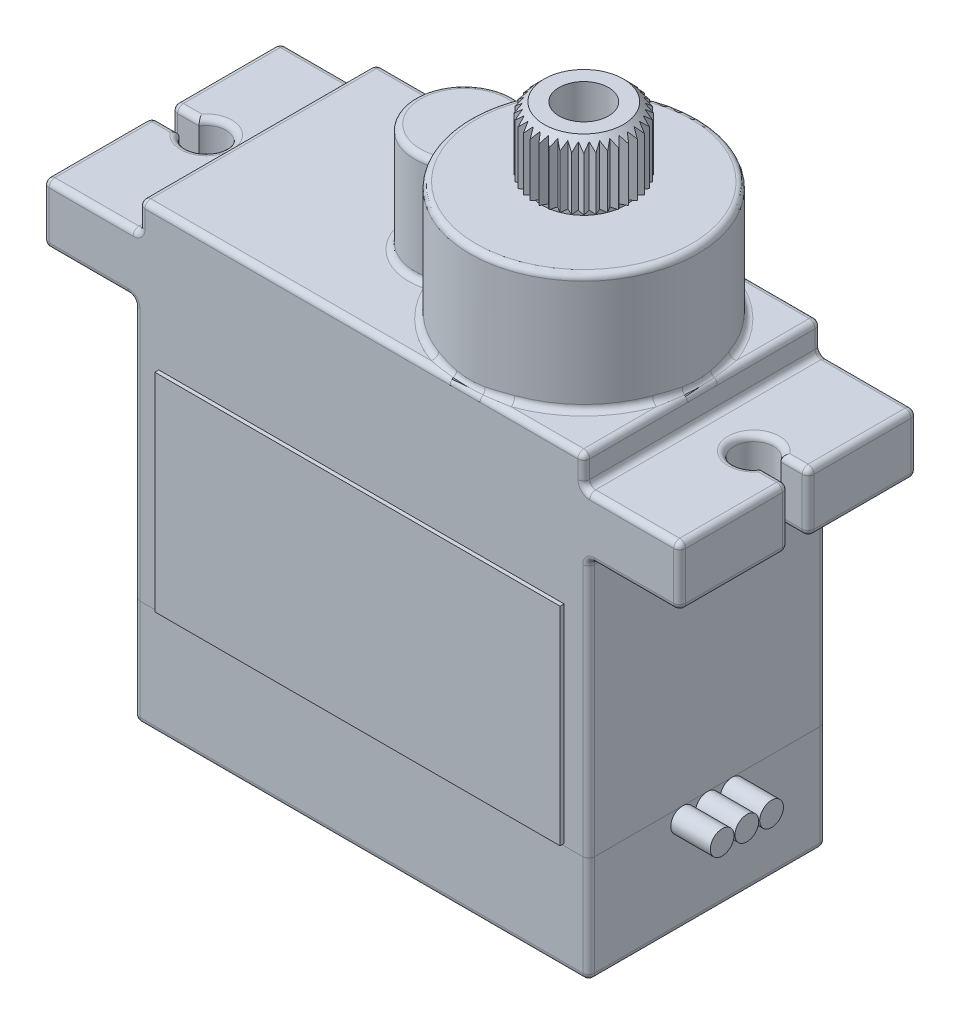
SolidWorks part; units mm, degrees
ref_plane "Front Plane" through (0, 0, 0) normal (0, 0, 1) x (1, 0, 0)
ref_plane "Top Plane" through (0, 0, 0) normal (0, 1, 0) x (1, 0, 0)
ref_plane "Right Plane" through (0, 0, 0) normal (1, 0, 0) x (0, 0, -1)
sketch "Sketch1" plane through (0, 0, 0) normal (0, 1, 0) x (1, 0, 0)
  line L1 (-11.5, -6) -> (11.5, -6)
  line L2 (-11.5, -6) -> (-11.5, 6)
  line L3 (-11.5, 6) -> (11.5, 6)
  line L4 (11.5, -6) -> (11.5, 6)
  line L5 (-11.5, -6) -> (11.5, 6) construction
  line L6 (-11.5, 6) -> (11.5, -6) construction
  point P0 (0, 0)
  dimension "D1" = 12
  dimension "D2" = 23
extrude "Boss-Extrude1" add sketch "Sketch1" along normal blind 18.5
sketch "Sketch2" plane through (0, 18.5, 0) normal (0, 1, 0) x (1, 0, 0)
  line L0 (11.5, 6) -> (-11.5, 6) construction
  line L1 (-16.1, -6) -> (16.1, -6)
  line L2 (-16.1, -6) -> (-16.1, 6)
  line L3 (-16.1, 6) -> (16.1, 6)
  line L4 (16.1, -6) -> (16.1, 6)
  line L5 (-16.1, -6) -> (16.1, 6) construction
  line L6 (-16.1, 6) -> (16.1, -6) construction
  point P0 (0, 0)
  dimension "D1" = 32.2
extrude "Boss-Extrude2" add sketch "Sketch2" along normal blind 3
sketch "Sketch3" plane through (0, 21.5, 0) normal (0, 1, 0) x (1, 0, 0)
  line L0 (16.1, 6) -> (-16.1, 6) construction
  line L1 (-11.25, -6) -> (11.25, -6)
  line L2 (-11.25, -6) -> (-11.25, 6)
  line L3 (-11.25, 6) -> (11.25, 6)
  line L4 (11.25, -6) -> (11.25, 6)
  line L5 (-11.25, -6) -> (11.25, 6) construction
  line L6 (-11.25, 6) -> (11.25, -6) construction
  point P0 (0, 0)
  dimension "D1" = 22.5
extrude "Boss-Extrude3" add sketch "Sketch3" along normal blind 1.5
sketch "Sketch4" plane through (0, 23, 0) normal (0, 1, 0) x (1, 0, 0)
  line L0 (-11.25, 6) -> (-11.25, -6) construction
  line L1 (5.25, 5.75) -> (5.25, 6) construction
  line L2 (11.25, 6) -> (-11.25, 6) construction
  line L3 (11, 0) -> (11.25, 0) construction
  line L4 (11.25, -6) -> (11.25, 6) construction
  line L5 (5.25, -5.75) -> (5.25, -6) construction
  line L6 (-11.25, -6) -> (11.25, -6) construction
  circle A0 centre (5.25, 0) radius 5.75
  point P5 (-11.25, 0)
  dimension "D1" = 11.5
extrude "Boss-Extrude4" add sketch "Sketch4" along normal blind 6
sketch "Sketch5" plane through (0, 23, 0) normal (0, 1, 0) x (1, 0, 0)
  line L0 (-11.25, 6) -> (-11.25, -6) construction
  circle A0 centre (-0.8, 0) radius 2.5
  circle A1 centre (5.25, 0) radius 5.75 construction
  circle A2 centre (5.25, 0) radius 5.75 construction
  point P2 (-3.3, 0)
  point P5 (-11.25, 0)
  point P6 (11, 0)
  dimension "D1" = 5
  dimension "D2" = 14.3
extrude "Boss-Extrude5" add sketch "Sketch5" along normal blind 5.5
sketch "Sketch6" plane through (0, 21.5, 0) normal (0, 1, 0) x (1, 0, 0)
  line L0 (-11.25, 6) -> (-11.25, -6) construction
  line L1 (0, 6) -> (0, -6) construction
  line L2 (11.25, 6) -> (-11.25, 6) construction
  line L3 (-11.25, -6) -> (11.25, -6) construction
  line L4 (-14.716, 0.5) -> (-16.1, 0.5)
  line L5 (-16.1, 6) -> (-16.1, -6) construction
  line L6 (-14.716, -0.5) -> (-16.1, -0.5)
  line L7 (-16.1, 0.5) -> (-16.1, -0.5)
  line L8 (16.1, 0.5) -> (16.1, -0.5)
  line L9 (14.716, -0.5) -> (16.1, -0.5)
  line L10 (14.716, 0.5) -> (16.1, 0.5)
  arc A0 (-14.716, -0.5) -> (-14.716, 0.5) centre (-13.85, 0) ccw
  arc A1 (14.716, -0.5) -> (14.716, 0.5) centre (13.85, 0) cw
  point P4 (-11.25, 0)
  dimension "D1" = 2
  dimension "D2" = 27.7
  dimension "D3" = 1
extrude "Cut-Extrude1" cut sketch "Sketch6" against normal through all
sketch "Sketch7" plane through (0, 29, 0) normal (0, 1, 0) x (1, 0, 0)
  circle A0 centre (5.25, 0) radius 2.5
  dimension "D1" = 5
extrude "Boss-Extrude6" add sketch "Sketch7" along normal blind 3.5
sketch "Sketch8" plane through (11.5, 0, 0) normal (1, 0, 0) x (0, 0, -1)
  line L0 (-1.25, 4.8) -> (1.25, 4.8) construction
  line L1 (-6, 0) -> (6, 0) construction
  circle A0 centre (-1.25, 4.8) radius 0.6
  circle A1 centre (0, 4.8) radius 0.6
  circle A2 centre (1.25, 4.8) radius 0.6
  dimension "D1" = 1.2
  dimension "D2" = 4.8
  dimension "D3" = 2.5
extrude "Boss-Extrude8" add sketch "Sketch8" along normal blind 2
fillet "Fillet1" radius 0.3 56 edges at (11.5, 0, 0) (11.5, 18.5, 0) (15.408, 18.5, 0.5) (12.85, 18.5, 0) (15.408, 18.5, -0.5) (15.408, 21.5, 0.5) (15.408, 21.5, -0.5) (12.85, 21.5, 0) (-11.25, 23, 0) (-15.408, 21.5, -0.5) (-11.25, 21.5, 0) (-15.408, 21.5, 0.5) (-12.85, 21.5, 0) (-16.1, 20, 0.5) (-16.1, 21.5, 3.25) (-16.1, 21.5, -3.25) (-16.1, 20, -0.5) (-16.1, 18.5, 3.25) (-16.1, 18.5, -3.25) (-15.408, 18.5, -0.5) (-12.85, 18.5, 0) (-15.408, 18.5, 0.5) (-11.5, 18.5, 0) (-11.5, 0, 0) (11.25, 23, 0) (11.25, 21.5, 0) (16.1, 21.5, 3.25) (16.1, 20, 0.5) (16.1, 18.5, 3.25) (16.1, 18.5, -3.25) (16.1, 20, -0.5) (16.1, 21.5, -3.25) (11.5, 9.25, -6) (13.8, 18.5, -6) (16.1, 20, -6) (13.675, 21.5, -6) (11.25, 22.25, -6) (0, 23, -6) (-11.25, 22.25, -6) (-13.675, 21.5, -6) (-16.1, 20, -6) (-13.8, 18.5, -6) (-11.5, 9.25, -6) (0, 0, -6) (-11.5, 9.25, 6) (-13.8, 18.5, 6) (-16.1, 20, 6) (-13.675, 21.5, 6) (-11.25, 22.25, 6) (0, 23, 6) (11.25, 22.25, 6) (13.675, 21.5, 6) (16.1, 20, 6) (13.8, 18.5, 6) (11.5, 9.25, 6) (0, 0, 6)
fillet "Fillet2" radius 0.3 10 edges at (5.25, 23, 5.75) (9.3159, 23, 4.0659) (11, 23, 0) (9.3159, 23, -4.0659) (5.25, 23, -5.75) (-3.3, 23, 0) (1.8189, 23, 4.6141) (1.8189, 23, -4.6141) (5.25, 29, 5.75) (-3.3, 28.5, 0)
chamfer "Chamfer1" distance 0.5 angle 45 1 edges at (5.25, 32.5, 2.5)
sketch "Sketch10" plane through (0, 32.5, 0) normal (0, 1, 0) x (1, 0, 0)
  line L0 (5.25, 0) -> (5.0321, 2.4905) construction
  line L1 (5.25, 0) -> (5.4679, 2.4905) construction
  line L2 (5.25, 0) -> (5.25, 2.5) construction
  line L3 (5.0321, 2.4905) -> (5.25, 2.2)
  line L4 (5.25, 2.2) -> (5.4679, 2.4905)
  line L5 (5.632, 2.1666) -> (5.897, 2.4148)
  line L6 (5.4679, 2.4905) -> (5.632, 2.1666)
  line L7 (6.0024, 2.0673) -> (6.3065, 2.2658)
  line L8 (5.897, 2.4148) -> (6.0024, 2.0673)
  line L9 (6.35, 1.9053) -> (6.6839, 2.0479)
  line L10 (6.3065, 2.2658) -> (6.35, 1.9053)
  line L11 (6.6641, 1.6853) -> (7.0178, 1.7678)
  line L12 (6.6839, 2.0479) -> (6.6641, 1.6853)
  line L13 (6.9353, 1.4141) -> (7.2979, 1.4339)
  line L14 (7.0178, 1.7678) -> (6.9353, 1.4141)
  line L15 (7.1553, 1.1) -> (7.5158, 1.0565)
  line L16 (7.2979, 1.4339) -> (7.1553, 1.1)
  line L17 (7.3173, 0.7524) -> (7.6648, 0.647)
  line L18 (7.5158, 1.0565) -> (7.3173, 0.7524)
  line L19 (7.4166, 0.382) -> (7.7405, 0.2179)
  line L20 (7.6648, 0.647) -> (7.4166, 0.382)
  line L21 (7.45, 0) -> (7.7405, -0.2179)
  line L22 (7.7405, 0.2179) -> (7.45, 0)
  line L23 (7.4166, -0.382) -> (7.6648, -0.647)
  line L24 (7.7405, -0.2179) -> (7.4166, -0.382)
  line L25 (7.3173, -0.7524) -> (7.5158, -1.0565)
  line L26 (7.6648, -0.647) -> (7.3173, -0.7524)
  line L27 (7.1553, -1.1) -> (7.2979, -1.4339)
  line L28 (7.5158, -1.0565) -> (7.1553, -1.1)
  line L29 (6.9353, -1.4141) -> (7.0178, -1.7678)
  line L30 (7.2979, -1.4339) -> (6.9353, -1.4141)
  line L31 (6.6641, -1.6853) -> (6.6839, -2.0479)
  line L32 (7.0178, -1.7678) -> (6.6641, -1.6853)
  line L33 (6.35, -1.9053) -> (6.3065, -2.2658)
  line L34 (6.6839, -2.0479) -> (6.35, -1.9053)
  line L35 (6.0024, -2.0673) -> (5.897, -2.4148)
  line L36 (6.3065, -2.2658) -> (6.0024, -2.0673)
  line L37 (5.632, -2.1666) -> (5.4679, -2.4905)
  line L38 (5.897, -2.4148) -> (5.632, -2.1666)
  line L39 (5.25, -2.2) -> (5.0321, -2.4905)
  line L40 (5.4679, -2.4905) -> (5.25, -2.2)
  line L41 (4.868, -2.1666) -> (4.603, -2.4148)
  line L42 (5.0321, -2.4905) -> (4.868, -2.1666)
  line L43 (4.4976, -2.0673) -> (4.1935, -2.2658)
  line L44 (4.603, -2.4148) -> (4.4976, -2.0673)
  line L45 (4.15, -1.9053) -> (3.8161, -2.0479)
  line L46 (4.1935, -2.2658) -> (4.15, -1.9053)
  line L47 (3.8359, -1.6853) -> (3.4822, -1.7678)
  line L48 (3.8161, -2.0479) -> (3.8359, -1.6853)
  line L49 (3.5647, -1.4141) -> (3.2021, -1.4339)
  line L50 (3.4822, -1.7678) -> (3.5647, -1.4141)
  line L51 (3.3447, -1.1) -> (2.9842, -1.0565)
  line L52 (3.2021, -1.4339) -> (3.3447, -1.1)
  line L53 (3.1827, -0.7524) -> (2.8352, -0.647)
  line L54 (2.9842, -1.0565) -> (3.1827, -0.7524)
  line L55 (3.0834, -0.382) -> (2.7595, -0.2179)
  line L56 (2.8352, -0.647) -> (3.0834, -0.382)
  line L57 (3.05, 0) -> (2.7595, 0.2179)
  line L58 (2.7595, -0.2179) -> (3.05, 0)
  line L59 (3.0834, 0.382) -> (2.8352, 0.647)
  line L60 (2.7595, 0.2179) -> (3.0834, 0.382)
  line L61 (3.1827, 0.7524) -> (2.9842, 1.0565)
  line L62 (2.8352, 0.647) -> (3.1827, 0.7524)
  line L63 (3.3447, 1.1) -> (3.2021, 1.4339)
  line L64 (2.9842, 1.0565) -> (3.3447, 1.1)
  line L65 (3.5647, 1.4141) -> (3.4822, 1.7678)
  line L66 (3.2021, 1.4339) -> (3.5647, 1.4141)
  line L67 (3.8359, 1.6853) -> (3.8161, 2.0479)
  line L68 (3.4822, 1.7678) -> (3.8359, 1.6853)
  line L69 (4.15, 1.9053) -> (4.1935, 2.2658)
  line L70 (3.8161, 2.0479) -> (4.15, 1.9053)
  line L71 (4.4976, 2.0673) -> (4.603, 2.4148)
  line L72 (4.1935, 2.2658) -> (4.4976, 2.0673)
  line L73 (4.868, 2.1666) -> (5.0321, 2.4905)
  line L74 (4.603, 2.4148) -> (4.868, 2.1666)
  circle A0 centre (5.25, 0) radius 2.5 construction
  arc A1 (5.4679, 2.4905) -> (5.0321, 2.4905) centre (5.25, 0) ccw
  circle A2 centre (5.25, 0) radius 2.2 construction
  arc A3 (5.897, 2.4148) -> (5.4679, 2.4905) centre (5.25, 0) ccw
  arc A4 (6.3065, 2.2658) -> (5.897, 2.4148) centre (5.25, 0) ccw
  arc A5 (6.6839, 2.0479) -> (6.3065, 2.2658) centre (5.25, 0) ccw
  arc A6 (7.0178, 1.7678) -> (6.6839, 2.0479) centre (5.25, 0) ccw
  arc A7 (7.2979, 1.4339) -> (7.0178, 1.7678) centre (5.25, 0) ccw
  arc A8 (7.5158, 1.0565) -> (7.2979, 1.4339) centre (5.25, 0) ccw
  arc A9 (7.6648, 0.647) -> (7.5158, 1.0565) centre (5.25, 0) ccw
  arc A10 (7.7405, 0.2179) -> (7.6648, 0.647) centre (5.25, 0) ccw
  arc A11 (7.7405, -0.2179) -> (7.7405, 0.2179) centre (5.25, 0) ccw
  arc A12 (7.6648, -0.647) -> (7.7405, -0.2179) centre (5.25, 0) ccw
  arc A13 (7.5158, -1.0565) -> (7.6648, -0.647) centre (5.25, 0) ccw
  arc A14 (7.2979, -1.4339) -> (7.5158, -1.0565) centre (5.25, 0) ccw
  arc A15 (7.0178, -1.7678) -> (7.2979, -1.4339) centre (5.25, 0) ccw
  arc A16 (6.6839, -2.0479) -> (7.0178, -1.7678) centre (5.25, 0) ccw
  arc A17 (6.3065, -2.2658) -> (6.6839, -2.0479) centre (5.25, 0) ccw
  arc A18 (5.897, -2.4148) -> (6.3065, -2.2658) centre (5.25, 0) ccw
  arc A19 (5.4679, -2.4905) -> (5.897, -2.4148) centre (5.25, 0) ccw
  arc A20 (5.0321, -2.4905) -> (5.4679, -2.4905) centre (5.25, 0) ccw
  arc A21 (4.603, -2.4148) -> (5.0321, -2.4905) centre (5.25, 0) ccw
  arc A22 (4.1935, -2.2658) -> (4.603, -2.4148) centre (5.25, 0) ccw
  arc A23 (3.8161, -2.0479) -> (4.1935, -2.2658) centre (5.25, 0) ccw
  arc A24 (3.4822, -1.7678) -> (3.8161, -2.0479) centre (5.25, 0) ccw
  arc A25 (3.2021, -1.4339) -> (3.4822, -1.7678) centre (5.25, 0) ccw
  arc A26 (2.9842, -1.0565) -> (3.2021, -1.4339) centre (5.25, 0) ccw
  arc A27 (2.8352, -0.647) -> (2.9842, -1.0565) centre (5.25, 0) ccw
  arc A28 (2.7595, -0.2179) -> (2.8352, -0.647) centre (5.25, 0) ccw
  arc A29 (2.7595, 0.2179) -> (2.7595, -0.2179) centre (5.25, 0) ccw
  arc A30 (2.8352, 0.647) -> (2.7595, 0.2179) centre (5.25, 0) ccw
  arc A31 (2.9842, 1.0565) -> (2.8352, 0.647) centre (5.25, 0) ccw
  arc A32 (3.2021, 1.4339) -> (2.9842, 1.0565) centre (5.25, 0) ccw
  arc A33 (3.4822, 1.7678) -> (3.2021, 1.4339) centre (5.25, 0) ccw
  arc A34 (3.8161, 2.0479) -> (3.4822, 1.7678) centre (5.25, 0) ccw
  arc A35 (4.1935, 2.2658) -> (3.8161, 2.0479) centre (5.25, 0) ccw
  arc A36 (4.603, 2.4148) -> (4.1935, 2.2658) centre (5.25, 0) ccw
  arc A37 (5.0321, 2.4905) -> (4.603, 2.4148) centre (5.25, 0) ccw
  point P114 (5.25, 0)
  dimension "D1" = 4.4
  dimension "D2" = 10
  dimension "D3" = 36
extrude "Cut-Extrude2" cut sketch "Sketch10" against normal up to surface (3.5 mm away) contours L69 A35 L70 | L67 A34 L68 | L65 A33 L66 | L63 A32 L64 | L61 A31 L62 | L59 A30 L60 | L57 A29 L58 | L55 A28 L56 | L53 A27 L54 | L51 A26 L52 | L49 A25 L50 | L45 A23 L46 | L43 A22 L44 | L41 A21 L42 | L39 A20 L40 | L37 A19 L38 | L35 A18 L36 | L33 A17 L34 | L31 A16 L32 | L29 A15 L30 | L27 A14 L28 | L25 A13 L26 | L23 A12 L24 | L21 A11 L22 | L19 A10 L20 | L17 A9 L18 | L15 A8 L16 | L13 A7 L14 | L11 A6 L12 | L9 A5 L10 | L7 A4 L8 | L5 A3 L6 | L4 A1 L3 | L73 A37 L74 | L71 A36 L72 | L47 A24 L48 region at (5.25, 32.5, -2.3979) region at (4.8336, 32.5, -2.3614) region at (5.6664, 32.5, -2.3614) region at (4.4299, 32.5, -2.2533) region at (6.0701, 32.5, -2.2533) region at (4.0511, 32.5, -2.0766) region at (6.4489, 32.5, -2.0766) region at (3.7087, 32.5, -1.8369) region at (6.7913, 32.5, -1.8369) region at (3.4131, 32.5, -1.5413) region at (7.0869, 32.5, -1.5413) region at (3.1734, 32.5, -1.1989) region at (7.3266, 32.5, -1.1989) region at (2.9967, 32.5, -0.8201) region at (7.5033, 32.5, -0.8201) region at (2.8886, 32.5, -0.4164) region at (7.6114, 32.5, -0.4164) region at (2.8521, 32.5, 0) region at (7.6479, 32.5, 0) region at (2.8886, 32.5, 0.4164) region at (7.6114, 32.5, 0.4164) region at (2.9967, 32.5, 0.8201) region at (7.5033, 32.5, 0.8201) region at (3.1734, 32.5, 1.1989) region at (7.3266, 32.5, 1.1989) region at (3.4131, 32.5, 1.5413) region at (7.0869, 32.5, 1.5413) region at (6.7913, 32.5, 1.8369) region at (4.0511, 32.5, 2.0766) region at (6.4489, 32.5, 2.0766) region at (4.4299, 32.5, 2.2533) region at (6.0701, 32.5, 2.2533) region at (4.8336, 32.5, 2.3614) region at (5.6664, 32.5, 2.3614) region at (5.25, 32.5, 2.3979) up to face at (5.25, 29, 5.45)
sketch "Sketch11" plane through (0, 0, 0) normal (0, 0, 1) x (1, 0, 0)
  line L0 (5.25, 32.5) -> (5.25, 27.5426) construction
  line L1 (7.9405, 29) -> (7.3405, 29)
  line L2 (7.9405, 29) -> (7.9405, 29.3)
  line L3 (7.9405, 29.3) -> (7.3405, 29.3)
  line L4 (7.3405, 29) -> (7.3405, 29.3)
  line L5 (7.25, 32.5) -> (3.25, 32.5) construction
  line L7 (10.7, 29) -> (-0.2, 29) construction
  line L8 (7.7405, 29) -> (7.7405, 32) construction
  dimension "D1" = 0.3
  dimension "D2" = 0.4
  dimension "D3" = 0.2
revolve "Cut-Revolve1" cut sketch "Sketch11" angle 360 about L0
sketch "Sketch12" plane through (0, 0, 6) normal (0, 0, 1) x (1, 0, 0)
  line L0 (11.2, 0) -> (-11.2, 0) construction
  line L1 (-10.25, 5.5) -> (10.25, 5.5)
  line L2 (-10.25, 5.5) -> (-10.25, 16)
  line L3 (-10.25, 16) -> (10.25, 16)
  line L4 (10.25, 5.5) -> (10.25, 16)
  line L5 (-10.25, 5.5) -> (10.25, 16) construction
  line L6 (-10.25, 16) -> (10.25, 5.5) construction
  point P0 (0, 10.75)
  dimension "D1" = 10.5
  dimension "D2" = 20.5
  dimension "D3" = 5.5
extrude "Boss-Extrude9" add sketch "Sketch12" along normal blind 0.2
sketch "Sketch13" plane through (0, 0, -6) normal (0, 0, -1) x (-1, 0, 0)
  line L4 (-10.25, 16) -> (-10.25, 5.5)
  line L5 (10.25, 16) -> (-10.25, 16)
  line L6 (10.25, 5.5) -> (10.25, 16)
  line L7 (-10.25, 5.5) -> (10.25, 5.5)
  line L8 (-10.25, 16) -> (-10.25, 5.5)
  line L9 (10.25, 16) -> (-10.25, 16)
  line L10 (10.25, 5.5) -> (10.25, 16)
  line L11 (-10.25, 5.5) -> (10.25, 5.5)
  dimension "D1" = 0
extrude "Boss-Extrude10" add sketch "Sketch13" along normal blind 0.2
ref_plane "Plane1" through (0, 5.4, 0) normal (0, 1, 0) x (1, 0, 0)
split line "Split Line1"
sketch "Sketch14" plane through (0, 32.5, 0) normal (0, 1, 0) x (1, 0, 0)
  circle A0 centre (5.25, 0) radius 1.25
  dimension "D1" = 2.5
extrude "Cut-Extrude3" cut sketch "Sketch14" against normal blind 2.5
sketch "Croquis1" plane through (0, 30, 0) normal (0, 1, 0) x (1, 0, 0)
  line L1 (4.5791, -1.0547) -> (5.9209, -1.0547)
  line L2 (4.5791, -1.0547) -> (4.5791, 1.0547)
  line L3 (4.5791, 1.0547) -> (5.9209, 1.0547)
  line L4 (5.9209, -1.0547) -> (5.9209, 1.0547)
  line L5 (4.5791, -1.0547) -> (5.9209, 1.0547) construction
  line L6 (4.5791, 1.0547) -> (5.9209, -1.0547) construction
  circle A0 centre (5.25, 0) radius 1.25 construction
  point P0 (5.25, 0)
extrude "Cortar-Extruir1" cut sketch "Croquis1" against normal blind 2
